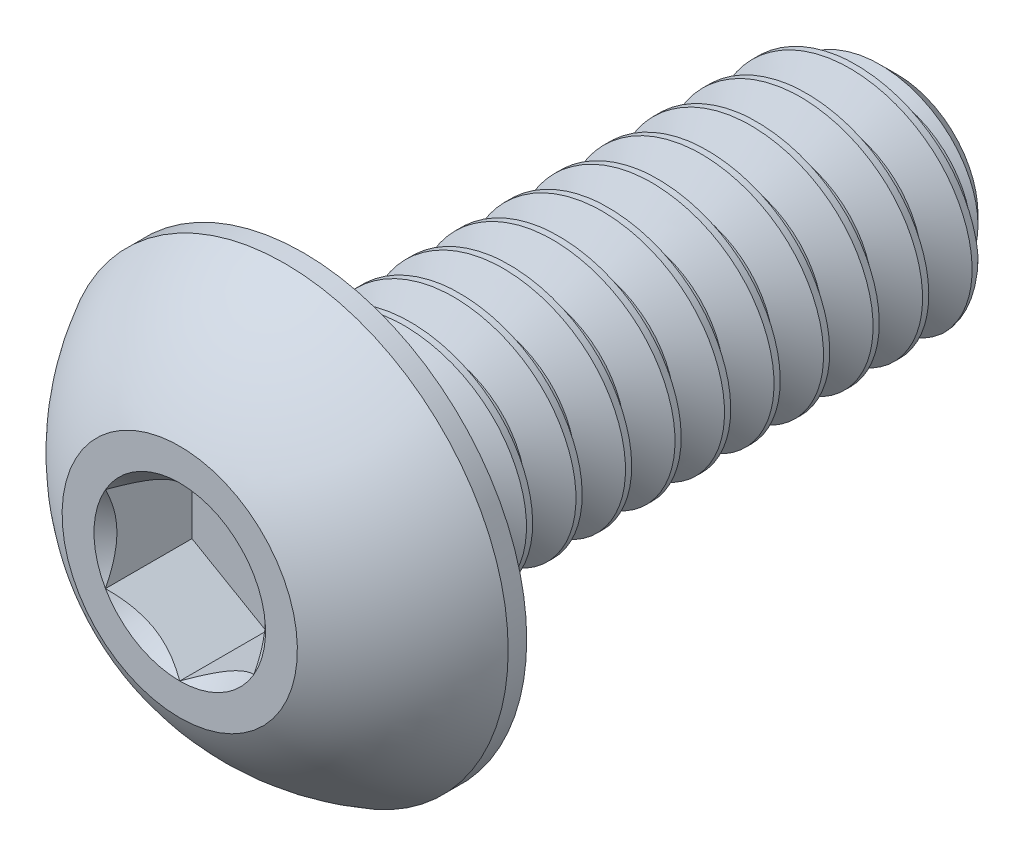
SolidWorks part; units mm, degrees
ref_plane "Front" through (0, 0, 0) normal (0, 0, 1) x (1, 0, 0)
ref_plane "Top" through (0, 0, 0) normal (0, 1, 0) x (1, 0, 0)
ref_plane "Right" through (0, 0, 0) normal (1, 0, 0) x (0, 0, -1)
sketch "Sketch1" plane through (0, 0, 0) normal (1, 0, 0) x (0, 0, -1)
  line L2 (1.3208, 1.2573) -> (7.6708, 1.2573)
  line L3 (7.6708, 1.2573) -> (7.6708, 0)
  line L4 (7.6708, 0) -> (1.3208, 0)
  line L6 (1.1227, 2.3876) -> (1.3208, 2.3876) construction
  line L7 (7.6708, 1.2573) -> (7.6708, -1.2573) construction
  line L8 (0, 0) -> (1.3208, 0) construction
  line L9 (1.3208, 2.3876) -> (1.3208, -2.3876) construction
  line L11 (1.3208, 1.2573) -> (1.3208, 0)
  line L13 (0, 0.7937) -> (0, -0.7937) construction
  line L14 (0, 0.7937) -> (0, 1.2573) construction
  arc A3 (0, 1.2573) -> (1.1227, 2.3876) centre (2.3962, 0) cw construction
  dimension "D1" = 0.1981
revolve "Revolve1" add sketch "Sketch1" angle 360 mid plane about L4
sketch "Sketch3" plane through (0, 0, -7.6708) normal (0, 0, -1) x (-1, 0, 0)
  circle A0 centre (0, 0) radius 1.2573
curve "Helix/Spiral1" pitch 0.5292 height 6.8792 radius 1.2573 centre (0, 0, -7.6708) axis (0, 0, 1) start towards (0, 1, 0)
sketch "Sketch2" plane through (0, 0, 0) normal (1, 0, 0) x (0, 0, -1)
  line L0 (7.6708, 1.2573) -> (8.1338, 1.2573)
  line L1 (8.1338, 1.2573) -> (7.9354, 0.9136)
  line L2 (7.9354, 0.9136) -> (7.8692, 0.9136)
  line L3 (7.8692, 0.9136) -> (7.6708, 1.2573)
  line L4 (7.77, 1.0854) -> (8.0346, 1.0854) construction
  dimension "D1" = 60
  dimension "D2" = 0.0661
  dimension "D3" = 0.2646
chamfer "Chamfer1" distance 0.3969 angle 45 1 edges at (0, 1.2573, -7.6708)
sweep "Cut-Sweep1" cut profiles "Sketch2" path "Helix/Spiral1" align with end faces yes
sketch "Sketch7" plane through (0, 0, 0) normal (1, 0, 0) x (0, 0, -1)
  line L6 (1.1227, 2.3876) -> (1.3208, 2.3876) construction
  line L8 (0, 0) -> (1.3208, 0) construction
  line L11 (1.3208, 2.3876) -> (1.3208, -2.3876) construction
  line L12 (1.1227, 2.3876) -> (1.3208, 2.3876)
  line L13 (0, 0) -> (1.3208, 0)
  line L14 (0, 0.7937) -> (0, -0.7937) construction
  line L15 (1.3208, 2.3876) -> (1.3208, 0)
  line L16 (0, 1.2573) -> (0, 0)
  arc A2 (1.1227, 2.3876) -> (0, 1.2573) centre (2.3962, 0) ccw construction
  arc A3 (1.1227, 2.3876) -> (0, 1.2573) centre (2.3962, 0) ccw
revolve "Revolve2" add sketch "Sketch7" angle 360 mid plane about L13
sketch "Sketch5" plane through (0, 0, 0) normal (0, 0, 1) x (1, 0, 0)
  line L1 (0.7937, -0.4583) -> (0.7937, 0.4583)
  line L2 (0.7937, 0.4583) -> (0, 0.9165)
  line L3 (0, 0.9165) -> (-0.7937, 0.4583)
  line L4 (-0.7937, 0.4583) -> (-0.7937, -0.4583)
  line L5 (-0.7937, -0.4583) -> (0, -0.9165)
  line L6 (0, -0.9165) -> (0.7937, -0.4583)
  circle A0 centre (0, 0) radius 0.7937 construction
extrude "Cut-Extrude2" cut sketch "Sketch5" against normal blind 0.9246
sketch "Sketch6" plane through (0, 0, 0) normal (0, 0, 1) x (1, 0, 0)
  circle A0 centre (0, 0) radius 0.9165
extrude "Cut-Extrude3" cut sketch "Sketch6" against normal blind 0.9246 draft 45
sketch "Sketch9" [suppressed] plane through (0, 0, -1.4986) normal (0, 0, 1) x (1, 0, 0)
  circle A2 centre (0, 0) radius 1.4224
extrude "Boss-Extrude2" [suppressed] add sketch "Sketch9" against normal offset from surface (12.7 mm away) 31.75 up to face at (0, 0.8604, -7.6708)
sketch "Sketch10" plane through (0, 0, 0) normal (1, 0, 0) x (0, 0, -1)
  line L0 (7.6708, 1.2573) -> (7.6708, -1.2573) construction
  point P0 (6.877, -1.2573)
  dimension "D1" = 0.7937
equation "\"D3@Helix/Spiral1\" = \"Lg@Sketch1\" + \"D4@Helix/Spiral1\""
equation "\"D2@Sketch2\" = \"D4@Helix/Spiral1\" * .125"
equation "\"D3@Sketch2\" = \"D4@Helix/Spiral1\" * .5"
equation "\"D1@Chamfer1\" = \"D4@Helix/Spiral1\" * .75"
equation "\"D1@Cut-Extrude2\" = \"Head Ht@Sketch1\" * .7"
equation "\"D1@Sketch1\" = \"Head Ht@Sketch1\" * .15"
equation "\"D1@Sketch10\" = \"D4@Helix/Spiral1\" * 1.5"
equation "\"D1@Cut-Extrude3\" = \"D1@Cut-Extrude2\""
